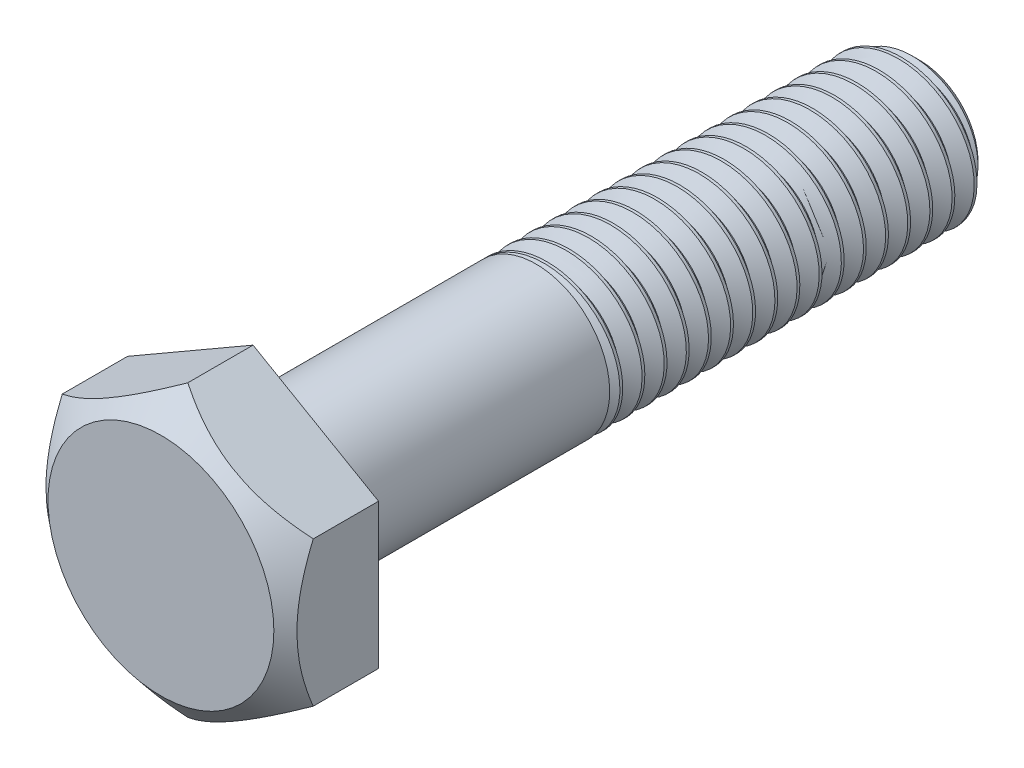
SolidWorks part; units mm, degrees
ref_plane "Front Plane" through (0, 0, 0) normal (0, 0, 1) x (1, 0, 0)
ref_plane "Top Plane" through (0, 0, 0) normal (0, 1, 0) x (1, 0, 0)
ref_plane "Right Plane" through (0, 0, 0) normal (1, 0, 0) x (0, 0, -1)
sketch "Sketch1" plane through (0, 0, 0) normal (1, 0, 0) x (0, 0, -1)
  line L0 (0, 0) -> (45, 0) construction
  line L1 (0, 0) -> (-6.4, 0) construction
  line L2 (45, 5) -> (45, -5) construction
  line L3 (-6.4, 8.5) -> (-6.4, -8.5) construction
  line L4 (0, 8.5) -> (0, -8.5) construction
  line L5 (44.9062, 5.1624) -> (46.4062, 5.1624) construction
  line L6 (46.4062, 5.1624) -> (45.6562, 3.8633) construction
  line L7 (45.6562, 3.8633) -> (44.9062, 5.1624) construction
  line L8 (44.9531, 5.0812) -> (46.3594, 5.0812) construction
  line L9 (45, 5) -> (46.3125, 5) construction
  line L10 (45.5625, 4.0257) -> (45.75, 4.0257) construction
  line L11 (45.6562, 4.0257) -> (45.6562, 3.8633) construction
  line L12 (45.6562, 5) -> (45.6562, 5.1624) construction
  point P6 (45, 0)
  point P10 (-6.4, 0)
  point P12 (0, 0)
  point P18 (39.75, -5)
  point P25 (45.6562, 5.0812)
  point P26 (19, 0)
  dimension "Thread Size" = 10
  dimension "Head Width" = 17
  dimension "Head Height" = 6.4
  dimension "Length" = 45
  dimension "D1" = 60
  dimension "Thread Pitch" = 1.5
  dimension "D2" = 0.1875
  dimension "D3" = 5.25
  dimension "Minimum Thread Length" = 26
sketch "Sketch2" plane through (0, 0, 0) normal (1, 0, 0) x (0, 0, -1)
  line L0 (45, 0) -> (0, 0)
  line L1 (45, 5) -> (45, -5) construction
  line L2 (0, 0) -> (0, 5)
  line L3 (0, 8.5) -> (0, -8.5) construction
  line L4 (0, 5) -> (43.95, 5)
  line L5 (43.95, 5) -> (45, 3.95)
  line L6 (45, 3.95) -> (45, 0)
  dimension "D1" = 1.05
  dimension "D2" = 45
revolve "Revolve1" add sketch "Sketch2" angle 360 about L0
sketch "Sketch3" plane through (0, 0, 0) normal (0, 0, 1) x (1, 0, 0)
  line L1 (0, 9.815) -> (-8.5, 4.9075)
  line L2 (-8.5, 4.9075) -> (-8.5, -4.9075)
  line L3 (-8.5, -4.9075) -> (0, -9.815)
  line L4 (0, -9.815) -> (8.5, -4.9075)
  line L5 (8.5, -4.9075) -> (8.5, 4.9075)
  line L6 (8.5, 4.9075) -> (0, 9.815)
  circle A0 centre (0, 0) radius 8.5 construction
extrude "Boss-Extrude1" add sketch "Sketch3" along normal up to vertex (6.4 mm away) up to point (0, 0, 6.4)
sketch "Sketch4" plane through (0, 0, 6.4) normal (0, 0, 1) x (1, 0, 0)
  circle A0 centre (0, 0) radius 7.65
  dimension "D1" = 15.3
extrude "Cut-Extrude1" cut sketch "Sketch4" against normal through all draft 50 flip side to cut
sketch "Sketch9" plane through (0, 0, 0) normal (0, 0, -1) x (-1, 0, 0)
  circle A0 centre (0, 0) radius 8.075
  circle A1 centre (0, 0) radius 9.815
  dimension "D1" = 16.15
extrude "Cut-Extrude2" cut sketch "Sketch9" against normal blind 0.16
sketch "Sketch5" plane through (0, 0, 0) normal (1, 0, 0) x (0, 0, -1)
  line L1 (19, 5) -> (19, -5) construction
  line L4 (45, 5) -> (45, -5) construction
  point P15 (19, 0)
split "Split1" bodies to split 115 resulting bodies 108 109 split by face at (-5, 0, 0)
sketch "Sketch6" plane through (0, 0, 0) normal (1, 0, 0) x (0, 0, -1)
  line L0 (44.9531, 5.0812) -> (46.3594, 5.0812)
  line L1 (46.3594, 5.0812) -> (45.75, 4.0257)
  line L2 (45.75, 4.0257) -> (45.5625, 4.0257)
  line L3 (45.5625, 4.0257) -> (44.9531, 5.0812)
sketch "Sketch7" plane through (0, 0, -45) normal (0, 0, -1) x (-1, 0, 0)
  circle A0 centre (0, 0) radius 5
curve "Helix/Spiral1" pitch 1.5 height 27.5 radius 5 centre (0, 0, -45) axis (0, 0, 1) start towards (0, 1, 0)
sweep "Cut-Sweep1" cut profiles "Sketch6" path "Helix/Spiral1" align with end faces yes
combine bodies "Combine1" operation type add bodies to combine 109 110
sketch "Sketch8" plane through (0, 0, 0) normal (1, 0, 0) x (0, 0, -1)
  line L0 (19, 0) -> (19, 5)
  line L1 (19, 5) -> (17.5, 5)
  line L2 (17.5, 5) -> (17.5, 0)
  line L3 (0, 0) -> (45, 0) construction
  line L4 (17.5, 0) -> (19, 0)
  line L5 (0, 5) -> (43.95, 5) construction
  dimension "D1" = 1.5
revolve "Revolve2" add sketch "Sketch8" angle 360 about L4
equation "\"D2@Sketch1\" = \"Thread Pitch@Sketch1\" / 8"
equation "\"D3@Sketch1\" = \"Thread Pitch@Sketch1\" * 3.5"
equation "\"D1@Sketch2\" = \"Thread Pitch@Sketch1\" * .7"
equation "\"D1@Sketch4\"=\"Head Width@Sketch1\"*.9"
equation "\"D3@Helix/Spiral1\" = \"Minimum Thread Length@Sketch1\" + \"Thread Pitch@Sketch1\""
equation "\"D4@Helix/Spiral1\" = \"Thread Pitch@Sketch1\""
equation "\"D1@Sketch8\" = \"Thread Pitch@Sketch1\""
equation "\"D1@Sketch9\"=\"Head Width@Sketch1\"*.95"
equation "\"D1@Cut-Extrude2\"=\"Head Height@Sketch1\"*.025"
